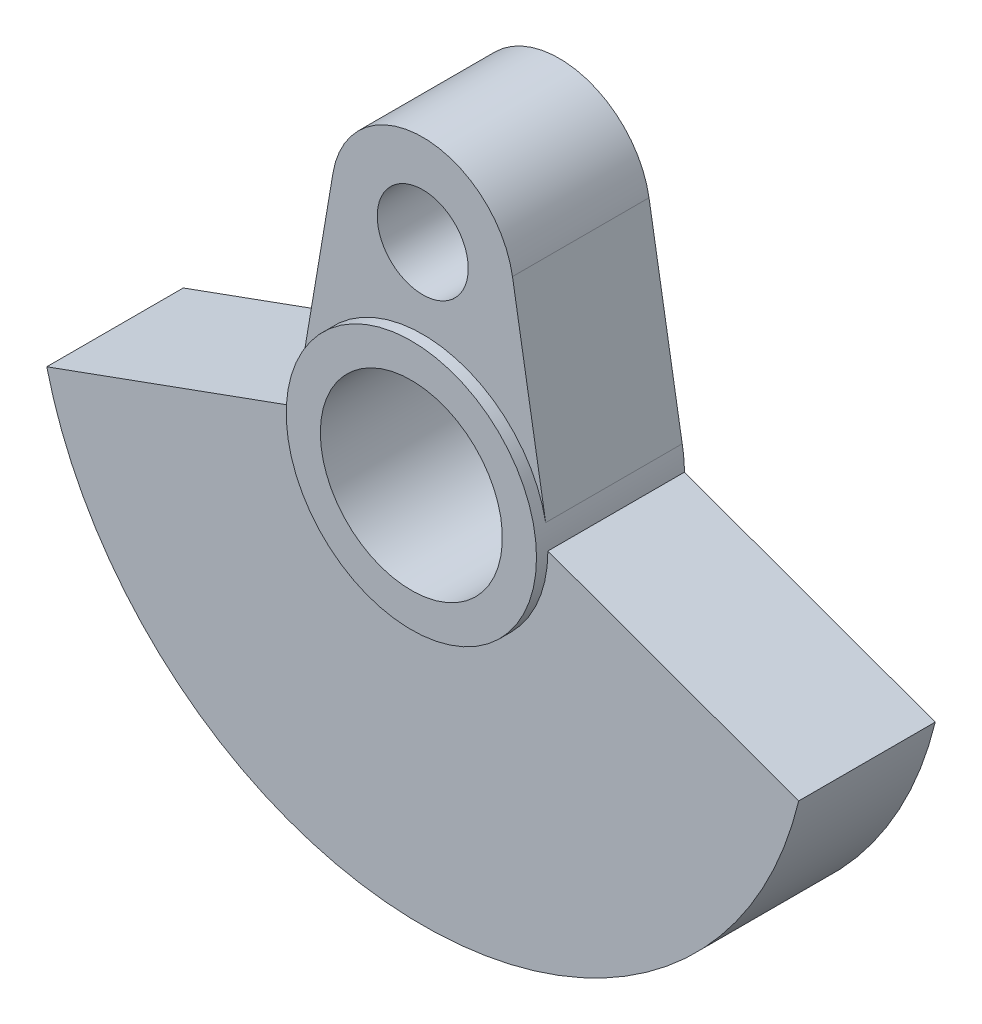
SolidWorks part; units mm, degrees
ref_plane "Ön Düzlem" through (0, 0, 0) normal (0, 0, 1) x (1, 0, 0)
ref_plane "Üst Düzlem" through (0, 0, 0) normal (0, 1, 0) x (1, 0, 0)
ref_plane "Sağ Düzlem" through (0, 0, 0) normal (1, 0, 0) x (0, 0, -1)
sketch "Sketch1" plane through (0, 0, 0) normal (0, 0, 1) x (1, 0, 0)
  line L0 (0, 38.2904) -> (0, -30.4826) construction
  line L1 (-50.0969, 0) -> (72.1147, 0) construction
  line L2 (-16.5227, -4) -> (-5.5, 0)
  line L3 (16.5227, -4) -> (5.5, 0)
  line L4 (-3.9441, 9.6667) -> (-5.4231, 0.9167)
  line L5 (3.9441, 9.6661) -> (5.4025, 1.0313)
  circle A0 centre (0, 0) radius 5.5
  arc A1 (3.9441, 9.6661) -> (-3.9441, 9.6667) centre (0, 9) ccw
  circle A2 centre (0, 9) radius 2
  arc A3 (16.5227, -4) -> (-16.5227, -4) centre (0, 0) cw
  circle A4 centre (0, 0) radius 4
  dimension "D1" = 11
  dimension "D2" = 8
  dimension "D3" = 4
  dimension "D4" = 17
  dimension "D5" = 4
  dimension "D6" = 9
extrude "Boss-Extrude1" add sketch "Sketch1" along normal mid plane 6 contours A3 L3 A0 L2 | L5 A1 L4 A0 A2 region at (0, -8.6209, 0) region at (-4.5236, 5.2646, 0)
extrude "Boss-Extrude4" add sketch "Sketch1<6>" along normal blind 6.5 from surface contours A0 A4 region at (-5.3257, 0.4469, 0) starting at face at (0, -6.625, -3)
sketch "Sketch1<6>" plane through (0, 0, 0) normal (0, 0, 1) x (1, 0, 0) same geometry as "Sketch1"
scale "Scale1" scale about centroid uniform scaling yes scale factor 1.5
